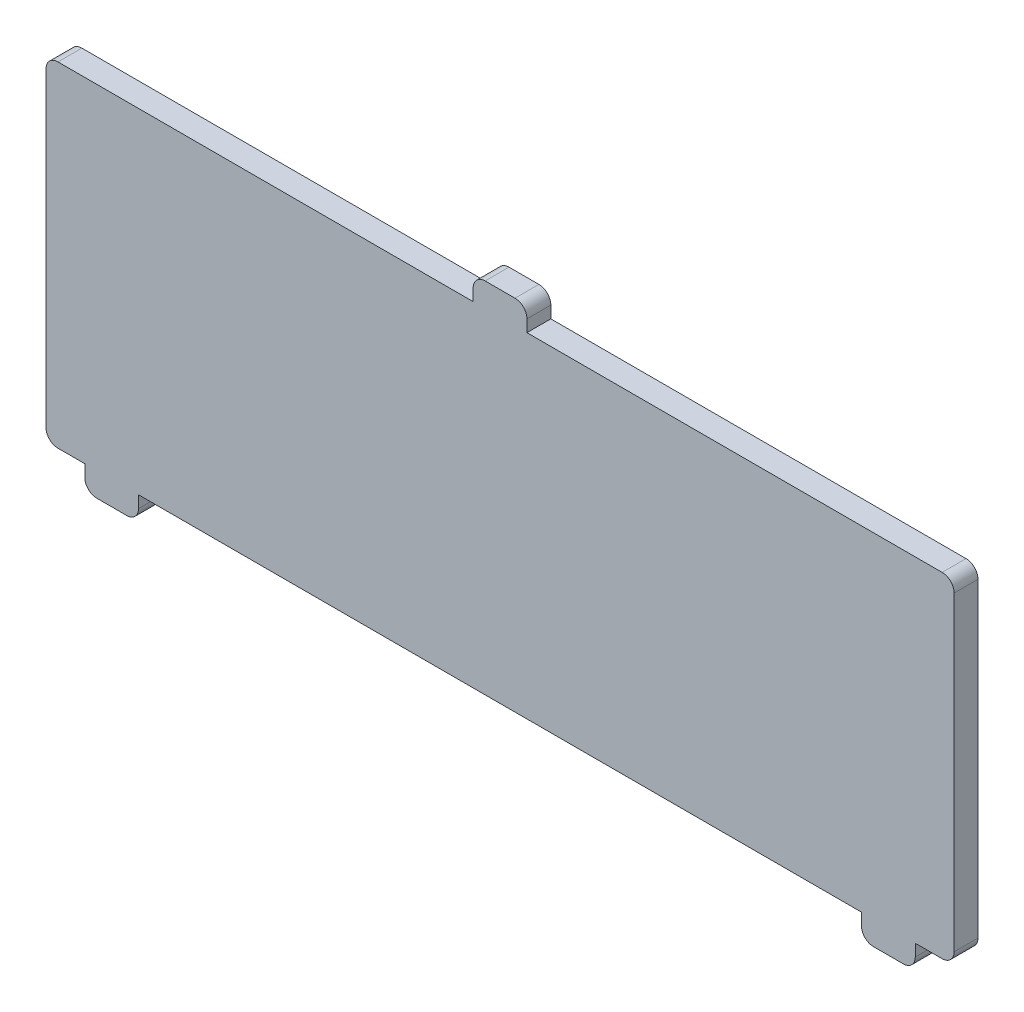
SolidWorks part; units mm, degrees
ref_plane "前基準面" through (0, 0, 0) normal (0, 0, 1) x (1, 0, 0)
ref_plane "上基準面" through (0, 0, 0) normal (0, 1, 0) x (1, 0, 0)
ref_plane "右基準面" through (0, 0, 0) normal (1, 0, 0) x (0, 0, -1)
sketch "Sketch1" plane through (0, 0, 0) normal (0, 0, 1) x (1, 0, 0)
  line L0 (0, 0) -> (0, 14) construction
  line L1 (-38, 14) -> (38, 14)
  line L2 (-38, 14) -> (-38, -14)
  line L3 (-38, -14) -> (38, -14)
  line L4 (38, 14) -> (38, -14)
  line L5 (-38, 14) -> (38, -14) construction
  line L6 (-38, -14) -> (38, 14) construction
  line L7 (0, 14) -> (0, -14) construction
  line L8 (-34.75, -14) -> (-30.25, -16) construction
  line L9 (-34.75, -14) -> (-30.25, -14)
  line L10 (-34.75, -14) -> (-34.75, -16)
  line L11 (-34.75, -16) -> (-30.25, -16)
  line L12 (-30.25, -14) -> (-30.25, -16)
  line L13 (-30.25, -14) -> (-29.5508, -16) construction
  line L14 (34.75, -16) -> (30.25, -16)
  line L15 (30.25, -14) -> (30.25, -16)
  line L16 (34.75, -14) -> (30.25, -14)
  line L17 (34.75, -14) -> (34.75, -16)
  line L18 (0, 0) -> (0, 22.3502) construction
  line L19 (-2.25, 16) -> (2.25, 14) construction
  line L20 (-2.25, 14) -> (2.25, 14)
  line L21 (-2.25, 14) -> (-2.25, 16)
  line L22 (-2.25, 16) -> (2.25, 16)
  line L23 (2.25, 14) -> (2.25, 16)
  line L24 (2.25, 16) -> (-2.25, 14) construction
  point P0 (0, 0)
  point P14 (-32.5, -15)
  point P24 (0, 15)
  dimension "D1" = 76
  dimension "D2" = 28
  dimension "D3" = 2
  dimension "D4" = 4.5
  dimension "D5" = 32.5
  dimension "D6" = 2
  dimension "D7" = 4.5
extrude "Boss-Extrude1" add sketch "Sketch1" along normal mid plane 2 contours L4 L1 L2 L3 | L12 L3 L10 L11 | L17 L3 L15 L14 | L23 L22 L21 L20 region at (0, 0, 0) region at (-32.5, -15, 0) region at (32.5, -15, 0)
fillet "Fillet1" radius 1 10 edges at (-38, 14, 0) (-30.25, -16, 0) (-34.75, -16, 0) (-38, -14, 0) (30.25, -16, 0) (34.75, -16, 0) (38, -14, 0) (38, 14, 0) (2.25, 16, 0) (-2.25, 16, 0)
